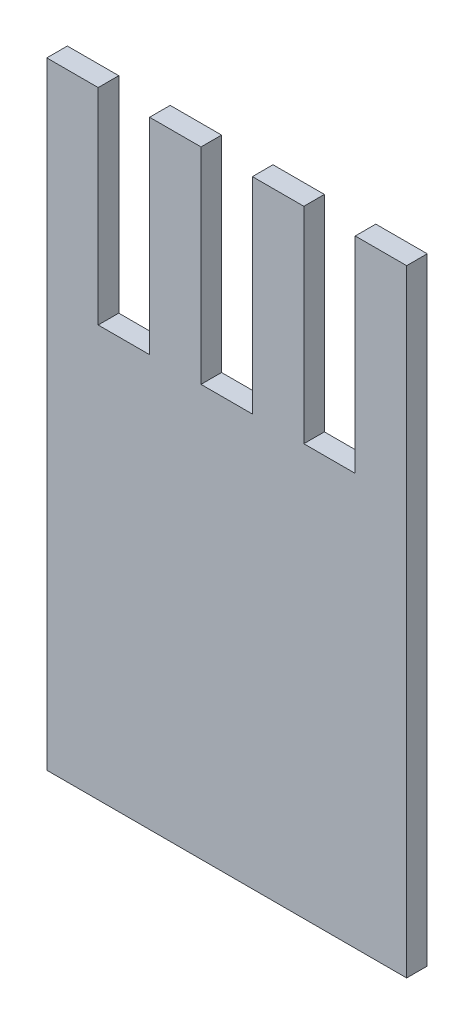
SolidWorks part; units mm, degrees
ref_plane "Front" through (0, 0, 0) normal (0, 0, 1) x (1, 0, 0)
ref_plane "Top" through (0, 0, 0) normal (0, 1, 0) x (1, 0, 0)
ref_plane "Side" through (0, 0, 0) normal (1, 0, 0) x (0, 0, -1)
sketch "Sketch1" plane through (0, 0, 0) normal (0, 0, 1) x (1, 0, 0)
  line L0 (-12.5, 30) -> (-17.5, 30)
  line L1 (17.5, 30) -> (12.5, 30)
  line L2 (17.5, 30) -> (17.5, -30)
  line L3 (17.5, -30) -> (-17.5, -30)
  line L4 (-17.5, 30) -> (-17.5, -30)
  line L5 (-2.5, 10) -> (2.5, 10)
  line L6 (-12.5, 10) -> (-7.5, 10)
  line L7 (-17.5, 30) -> (-12.5, 30)
  line L8 (-17.5, 30) -> (-17.5, 10)
  line L9 (-12.5, 10) -> (-7.5, 10)
  line L10 (17.5, 30) -> (17.5, 10)
  line L20 (-2.5, 30) -> (-2.5, 10)
  line L21 (-2.5, 10) -> (2.5, 10)
  line L22 (2.5, 30) -> (2.5, 10)
  line L24 (-7.5, 30) -> (-7.5, 10)
  line L25 (-7.5, 10) -> (-12.5, 10)
  line L26 (-12.5, 30) -> (-12.5, 10)
  line L28 (7.5, 30) -> (7.5, 10)
  line L29 (7.5, 10) -> (12.5, 10)
  line L30 (12.5, 30) -> (12.5, 10)
  line L31 (-7.5, 30) -> (-2.5, 30)
  line L32 (-17.5, 10) -> (-17.5, 0)
  line L33 (-2.5, 30) -> (-7.5, 30)
  line L34 (2.5, 30) -> (7.5, 30)
  line L35 (7.5, 30) -> (2.5, 30)
  line L36 (12.5, 30) -> (17.5, 30)
  line L37 (-17.5, 0) -> (17.5, 0)
  line L38 (17.5, 10) -> (17.5, 0)
  line L39 (-2.5, 10) -> (2.5, 10)
  line L40 (7.5, 10) -> (12.5, 10)
  line L41 (7.5, 10) -> (12.5, 10)
  point P0 (0, 0)
extrude "Boss-Extrude5" add sketch "Sketch1" along normal blind 2 contours L37 L4 L3 L2 region at (0, -15, 0)
extrude "Boss-Extrude6" add sketch "Sketch1<7>" along normal blind 2 contours L4 L37 L2 L1 L30 L29 L28 L34 L22 L5 L20 L31 L24 L6 L26 L0 region at (-12.961, 20, 0)
sketch "Sketch1<7>" plane through (0, 0, 0) normal (0, 0, 1) x (1, 0, 0) same geometry as "Sketch1"
